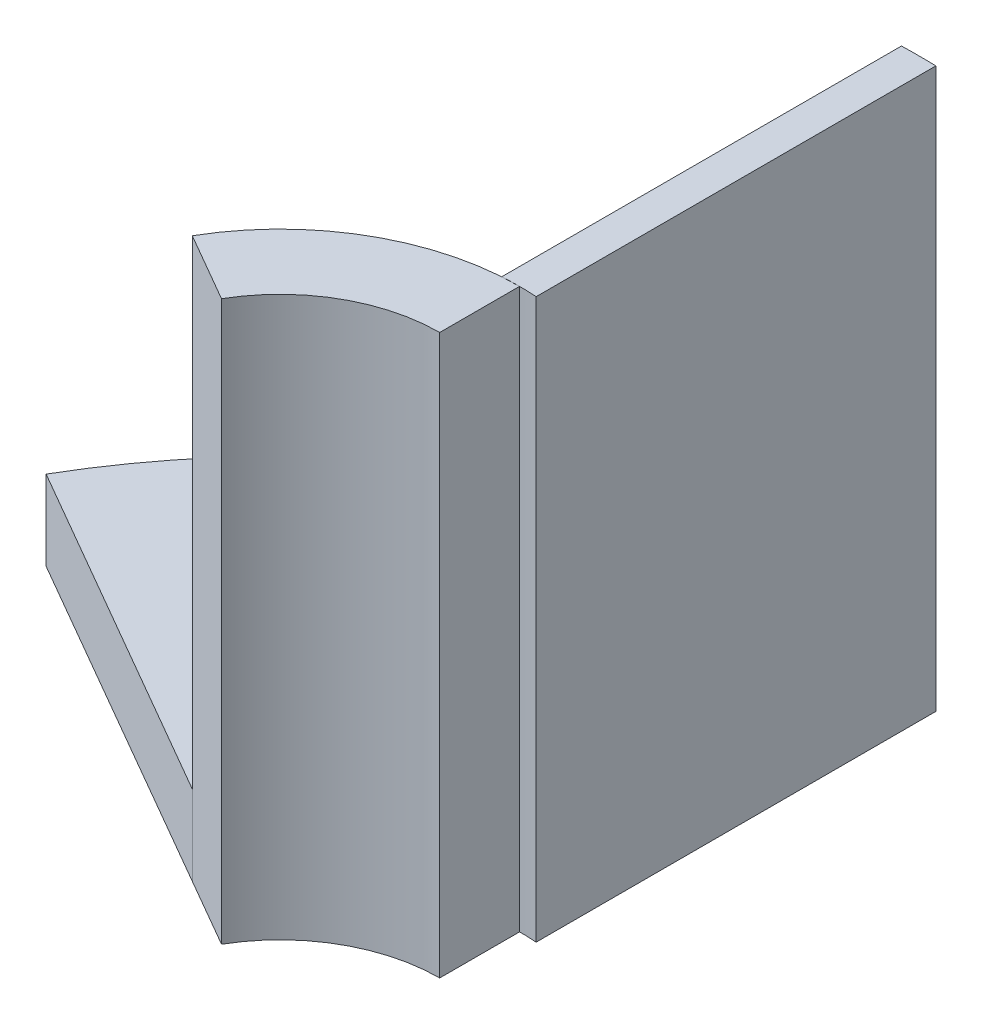
SolidWorks part; units mm, degrees
ref_plane "前视基准面" through (0, 0, 0) normal (0, 0, 1) x (1, 0, 0)
ref_plane "上视基准面" through (0, 0, 0) normal (0, 1, 0) x (1, 0, 0)
ref_plane "右视基准面" through (0, 0, 0) normal (1, 0, 0) x (0, 0, -1)
ref_plane "alpha1" through (0, 0, 0) normal (0, 1, 0) x (1, 0, 0)
ref_plane "alpha2" through (0, 5, 0) normal (0, 1, 0) x (1, 0, 0)
ref_plane "alpha3" through (0, 35, 0) normal (0, 1, 0) x (1, 0, 0)
ref_axis "axis0" through (0, -55, 0) along (0, 1, 0)
ref_axis "axis1" through (0, 0, 55) along (0, 0, -1)
sketch "草图1" plane through (0, 0, 0) normal (0, 1, 0) x (1, 0, 0)
  line L0 (0, 15) -> (0, 40)
  line L1 (-34.641, 20) -> (-12.9904, 7.5)
  arc A0 (0, 15) -> (-12.9904, 7.5) centre (0, 0) ccw
  arc A1 (0, 40) -> (-34.641, 20) centre (0, 0) ccw
extrude "底板" add sketch "草图1" along normal up to surface (5 mm away) from surface up to plane "alpha2" starting at plane "alpha1"
sketch "草图2" plane through (0, 0, 0) normal (0, 1, 0) x (1, 0, 0)
  line L0 (0, 10) -> (0, 15)
  line L2 (-8.6603, 5) -> (-12.9904, 7.5)
  arc A0 (0, 15) -> (-12.9904, 7.5) centre (0, 0) ccw
  arc A1 (0, 10) -> (-8.6603, 5) centre (0, 0) ccw
extrude "内板" add sketch "草图2" along normal up to surface (35 mm away) from surface separate body up to plane "alpha3" starting at plane "alpha1"
sketch "草图5" plane through (0, 0, 0) normal (0, 1, 0) x (1, 0, 0)
  line L0 (1.0778, 14.9612) -> (1.0778, 39.9855)
  line L5 (0, 40) -> (0, 15) construction
  line L8 (-1.0778, 14.9612) -> (-1.0778, 39.9855)
  arc A0 (1.0778, 14.9612) -> (-1.0778, 14.9612) centre (0, 0) ccw
  arc A1 (1.0778, 39.9855) -> (-1.0778, 39.9855) centre (0, 0) ccw
  point P0 (0, 0)
extrude "侧板" add sketch "草图5" along normal up to surface (35 mm away) from surface separate body up to plane "alpha3" starting at plane "alpha1"
